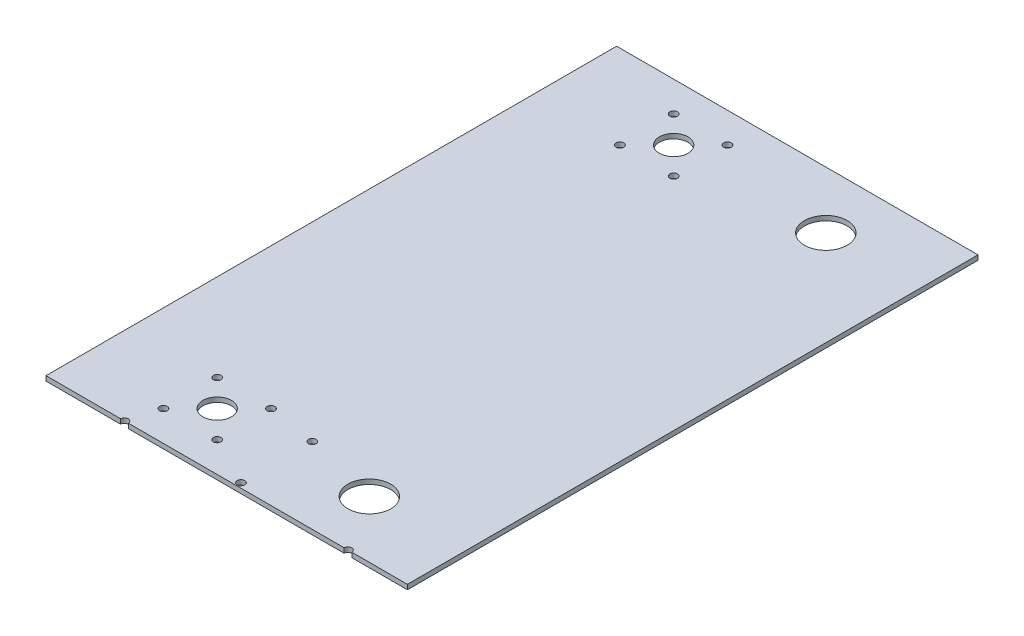
SolidWorks part; units mm, degrees
material "6061-T6 (SS)"
ref_plane "Front Plane" through (0, 0, 0) normal (0, 0, 1) x (1, 0, 0)
ref_plane "Top Plane" through (0, 0, 0) normal (0, 1, 0) x (1, 0, 0)
ref_plane "Right Plane" through (0, 0, 0) normal (1, 0, 0) x (0, 0, -1)
sketch "Sketch1" plane through (0, 0, 0) normal (0, 1, 0) x (1, 0, 0)
  line L1 (120.65, -190.5) -> (-120.65, -190.5)
  line L2 (120.65, -190.5) -> (120.65, 190.5)
  line L3 (120.65, 190.5) -> (-120.65, 190.5)
  line L4 (-120.65, -190.5) -> (-120.65, 190.5)
  line L5 (120.65, -190.5) -> (-120.65, 190.5) construction
  line L6 (120.65, 190.5) -> (-120.65, -190.5) construction
  point P0 (0, 0)
  dimension "D1" = 241.3
  dimension "D2" = 381
extrude "Boss-Extrude1" add sketch "Sketch1" along normal blind 3.175
sketch "Sketch6" plane through (0, 3.175, 0) normal (0, 1, 0) x (1, 0, 0)
  line L1 (-44.45, 152.4) -> (0, 0) construction
  line L2 (0, 0) -> (-44.45, -152.4) construction
  line L5 (-120.65, 190.5) -> (-120.65, -190.5) construction
  circle A0 centre (-44.45, -152.4) radius 38.1 construction
  circle A1 centre (-44.45, 152.4) radius 38.1 construction
  circle A2 centre (57.15, -152.4) radius 38.1 construction
  circle A3 centre (57.15, 152.4) radius 38.1 construction
  dimension "D1" = 76.2
  dimension "D5" = 228.6
  dimension "D3" = 101.6
  dimension "D4" = 76.2
sketch "Sketch7" plane through (0, 3.175, 0) normal (0, 1, 0) x (1, 0, 0)
  circle A0 centre (57.15, -152.4) radius 14.2875
  circle A1 centre (57.15, 152.4) radius 14.2875
  circle A2 centre (-44.45, 152.4) radius 9.525
  circle A3 centre (-44.45, -152.4) radius 9.525
  circle A4 centre (-62.4105, 170.3605) radius 2.5527
  circle A5 centre (-44.45, 152.4) radius 25.4 construction
  circle A6 centre (-26.4895, 170.3605) radius 2.5527
  circle A7 centre (-26.4895, 134.4395) radius 2.5527
  circle A8 centre (-62.4105, 134.4395) radius 2.5527
  circle A9 centre (-44.45, -152.4) radius 25.4 construction
  circle A10 centre (-62.4105, -134.4395) radius 2.5527
  circle A11 centre (-26.4895, -134.4395) radius 2.5527
  circle A12 centre (-26.4895, -170.3605) radius 2.5527
  circle A13 centre (-62.4105, -170.3605) radius 2.5527
  point P17 (0, 0)
  point P24 (-44.45, 152.4)
  point P25 (0, 0)
  point P27 (-44.45, -152.4)
  point P34 (-44.45, -152.4)
  dimension "D1" = 28.575
  dimension "D2" = 19.05
  dimension "D3" = 5.1054
  dimension "D5" = 50.8
  dimension "D4" = 4
  dimension "D6" = 4
extrude "Axle Holes" cut sketch "Sketch7" against normal through all
sketch "Sketch10" plane through (0, 3.175, 0) normal (0, 1, 0) x (1, 0, 0)
  circle A0 centre (6.35, -139.7) radius 2.5527 construction
  circle A1 centre (-68.2625, -190.5) radius 2.5527 construction
  circle A3 centre (6.35, -187.325) radius 2.5527 construction
  circle A4 centre (80.9625, -190.5) radius 2.5527 construction
  circle A5 centre (6.35, -139.7) radius 2.5527
  circle A6 centre (-68.2625, -190.5) radius 2.5527
  circle A8 centre (6.35, -187.325) radius 2.5527
  circle A9 centre (80.9625, -190.5) radius 2.5527
extrude "Cut-Extrude5" cut sketch "Sketch10" against normal through all
sketch "Sketch8" plane through (0, 3.175, 0) normal (0, 1, 0) x (1, 0, 0)
  circle A3 centre (38.8835, 28.8822) radius 19.8684
extrude "Cut-Extrude4" [suppressed] cut sketch "Sketch8" against normal through all
